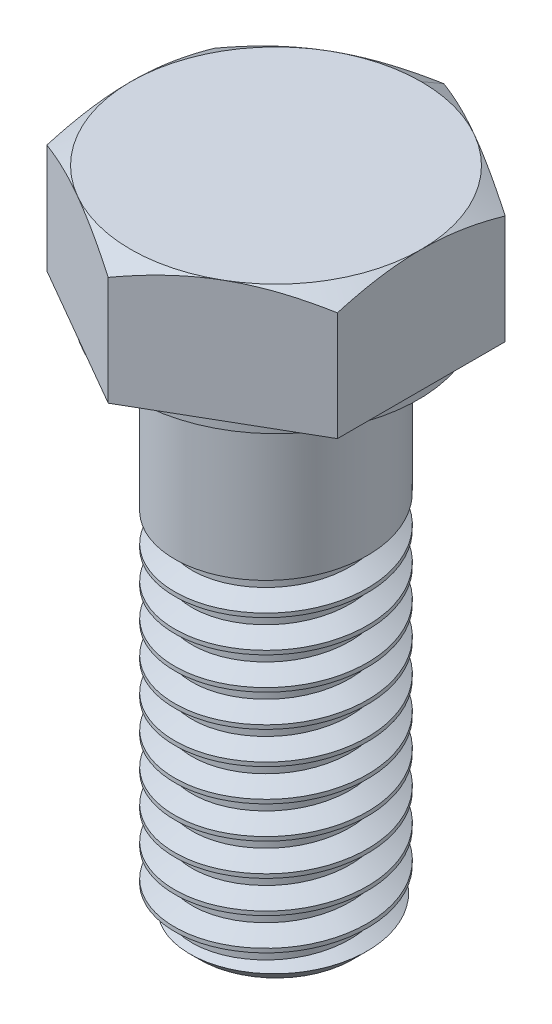
SolidWorks part; units mm, degrees
ref_plane "Front" through (0, 0, 0) normal (0, 0, 1) x (1, 0, 0)
ref_plane "Top" through (0, 0, 0) normal (0, 1, 0) x (1, 0, 0)
ref_plane "Right" through (0, 0, 0) normal (1, 0, 0) x (0, 0, -1)
sketch "Sketch1" plane through (0, 0, 0) normal (0, 1, 0) x (1, 0, 0)
  line L1 (0, 8.2561) -> (-7.15, 4.1281)
  line L2 (-7.15, 4.1281) -> (-7.15, -4.1281)
  line L3 (-7.15, -4.1281) -> (0, -8.2561)
  line L4 (0, -8.2561) -> (7.15, -4.1281)
  line L5 (7.15, -4.1281) -> (7.15, 4.1281)
  line L6 (7.15, 4.1281) -> (0, 8.2561)
  circle A0 centre (0, 0) radius 7.15 construction
  dimension "D1" = 14.3
extrude "Boss-Extrude1" add sketch "Sketch1" against normal blind 6
sketch "Sketch2" plane through (0, -6, 0) normal (0, -1, 0) x (1, 0, 0)
  circle A0 centre (0, 0) radius 7
  dimension "D1" = 14
extrude "Boss-Extrude2" add sketch "Sketch2" along normal blind 0.48
sketch "Sketch3" plane through (0, -6.48, 0) normal (0, -1, 0) x (1, 0, 0)
  circle A0 centre (0, 0) radius 4.745
  dimension "D1" = 9.49
extrude "Boss-Extrude3" add sketch "Sketch3" along normal blind 25.5
chamfer "Chamfer1" distance 1 angle 45 1 edges at (0, -31.98, -4.745)
sketch "Sketch4" plane through (0, 0, 0) normal (0, 1, 0) x (1, 0, 0)
  line L0 (7.15, 4.1281) -> (0, 8.2561) construction
  circle A0 centre (0, 0) radius 7.15
sketch "Sketch5" plane through (0, 0, 0) normal (1, 0, 0) x (0, 0, -1)
  line L0 (7.15, 0) -> (9.15, 0)
  line L1 (9.15, 0) -> (9.15, -1.1547)
  line L2 (9.15, -1.1547) -> (7.15, 0)
  dimension "D1" = 30
  dimension "D2" = 2
sweep "Cut-Sweep1" cut profiles "Sketch5" path "Sketch4"
sketch "Sketch6" plane through (0, -31.98, 0) normal (0, -1, 0) x (1, 0, 0)
  circle A0 centre (0, 0) radius 4.745
  circle A1 centre (0, 0) radius 4.745 construction
curve "Helix/Spiral1" pitch 1.5875 height 18.2562 radius 4.745 centre (0, -31.98, 0) axis (0, 1, 0) start towards (0, 0, -1)
sketch "Sketch7" plane through (0, 0, 0) normal (1, 0, 0) x (0, 0, -1)
  line L0 (-3.895, -32.4707) -> (-3.895, -32.8807)
  line L1 (-3.895, -32.8807) -> (-4.745, -33.3715)
  line L2 (-4.745, -33.3715) -> (-4.745, -31.98)
  line L3 (-4.745, -31.98) -> (-3.895, -32.4707)
  line L4 (-3.895, -32.6757) -> (-4.745, -32.6757) construction
  dimension "D1" = 0.41
  dimension "D2" = 0.85
  dimension "D3" = 60
sweep "Cut-Sweep2" cut profiles "Sketch7" path "Helix/Spiral1" align with end faces yes
sketch "Sketch8" plane through (0, 0, 0) normal (1, 0, 0) x (0, 0, -1)
  line L4 (3.895, -14.6245) -> (4.745, -15.1152)
  line L5 (4.745, -15.1152) -> (4.745, -13.7237)
  line L6 (4.745, -13.7237) -> (3.895, -14.2145)
  line L7 (3.895, -14.2145) -> (3.895, -14.6245)
  line L8 (3.895, -14.6245) -> (4.745, -15.1152)
  line L9 (4.745, -15.1152) -> (4.745, -13.7237)
  line L10 (4.745, -13.7237) -> (3.895, -14.2145)
  line L11 (3.895, -14.2145) -> (3.895, -14.6245)
  dimension "D1" = 0
extrude "Cut-Extrude1" cut sketch "Sketch8" against normal blind 10
